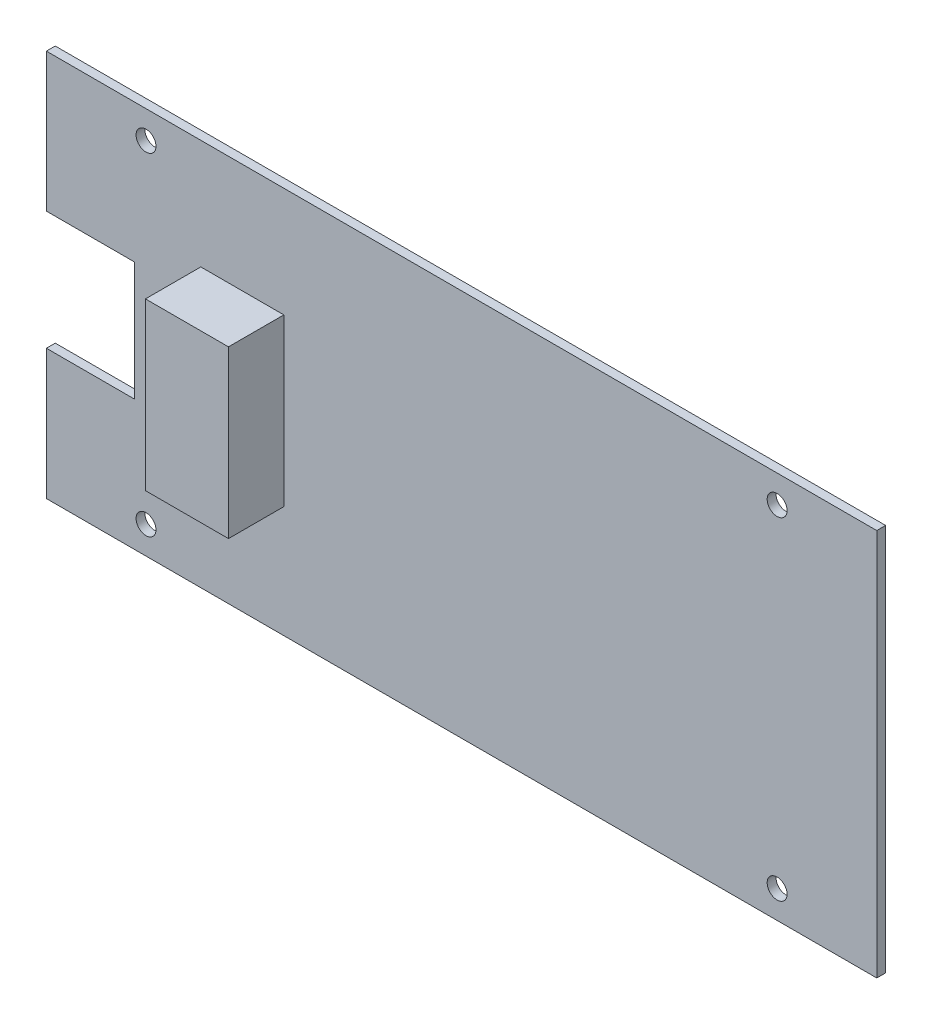
SolidWorks part; units mm, degrees
material "ﾏｲｸﾛﾌﾟﾛｾｯｻ搭載基板 (複雑)"
ref_plane "正面" through (0, 0, 0) normal (0, 0, 1) x (1, 0, 0)
ref_plane "平面" through (0, 0, 0) normal (0, 1, 0) x (1, 0, 0)
ref_plane "右側面" through (0, 0, 0) normal (1, 0, 0) x (0, 0, -1)
sketch "ｽｹｯﾁ1" plane through (0, 0, 0) normal (0, 0, 1) x (1, 0, 0)
  line L1 (-75, -35) -> (75, -35)
  line L2 (-75, -35) -> (-75, 35)
  line L3 (-75, 35) -> (75, 35)
  line L4 (75, -35) -> (75, 35)
  line L5 (-75, -35) -> (75, 35) construction
  line L6 (-75, 35) -> (75, -35) construction
  point P0 (0, 0)
  dimension "D1" = 150
  dimension "D2" = 70
extrude "ﾎﾞｽ - 押し出し1" add sketch "ｽｹｯﾁ1" along normal blind 1.6
hole_wizard "M3 すきま穴1" positions "ｽｹｯﾁ4" profile "ｽｹｯﾁ3" hole size "M3" standard "JIS" end condition through all
sketch "ｽｹｯﾁ4" plane through (0, 0, 1.6) normal (0, 0, 1) x (1, 0, 0)
  line L0 (-57, 30) -> (57, -30) construction
  line L2 (-57, -30) -> (57, 30) construction
  point P0 (57, 30)
  point P2 (57, -30)
  point P4 (-57, -30)
  point P6 (-57, 30)
  dimension "D1" = 114
  dimension "D2" = 60
sketch "ｽｹｯﾁ3" plane through (57, 30, 1.6) normal (1, 0, 0) x (0, -1, 0)
  line L0 (0, 0) -> (0, 1.6)
  line L1 (0, 1.6) -> (1.8, 1.6)
  line L2 (1.8, 1.6) -> (1.8, 0)
  line L5 (1.8, 0) -> (0, 0)
  line L11 (0, -6.35) -> (0, 107.95) construction
  dimension "通し穴の直径" = 3.6
  dimension "通し穴の深さ" = 1.6
sketch "ｽｹｯﾁ5" plane through (0, 0, 1.6) normal (0, 0, 1) x (1, 0, 0)
  line L1 (-94.8985, -11.479) -> (-59.1236, -11.479)
  line L2 (-94.8985, -11.479) -> (-94.8985, 9.9696)
  line L3 (-94.8985, 9.9696) -> (-59.1236, 9.9696)
  line L4 (-59.1236, -11.479) -> (-59.1236, 9.9696)
  line L5 (-94.8985, -11.479) -> (-59.1236, 9.9696) construction
  line L6 (-94.8985, 9.9696) -> (-59.1236, -11.479) construction
  point P0 (-77.0111, -0.7547)
extrude "ｶｯﾄ - 押し出し1" cut sketch "ｽｹｯﾁ5" against normal blind 10
sketch "ｽｹｯﾁ6" plane through (0, 0, 1.6) normal (0, 0, 1) x (1, 0, 0)
  line L1 (-47.1051, -14.814) -> (-32.1051, -14.814)
  line L2 (-47.1051, -14.814) -> (-47.1051, 15.186)
  line L3 (-47.1051, 15.186) -> (-32.1051, 15.186)
  line L4 (-32.1051, -14.814) -> (-32.1051, 15.186)
  line L5 (-47.1051, -14.814) -> (-32.1051, 15.186) construction
  line L6 (-47.1051, 15.186) -> (-32.1051, -14.814) construction
  point P0 (-39.6051, 0.186)
  dimension "D1" = 30
  dimension "D2" = 15
extrude "ﾎﾞｽ - 押し出し2" add sketch "ｽｹｯﾁ6" along normal blind 10
